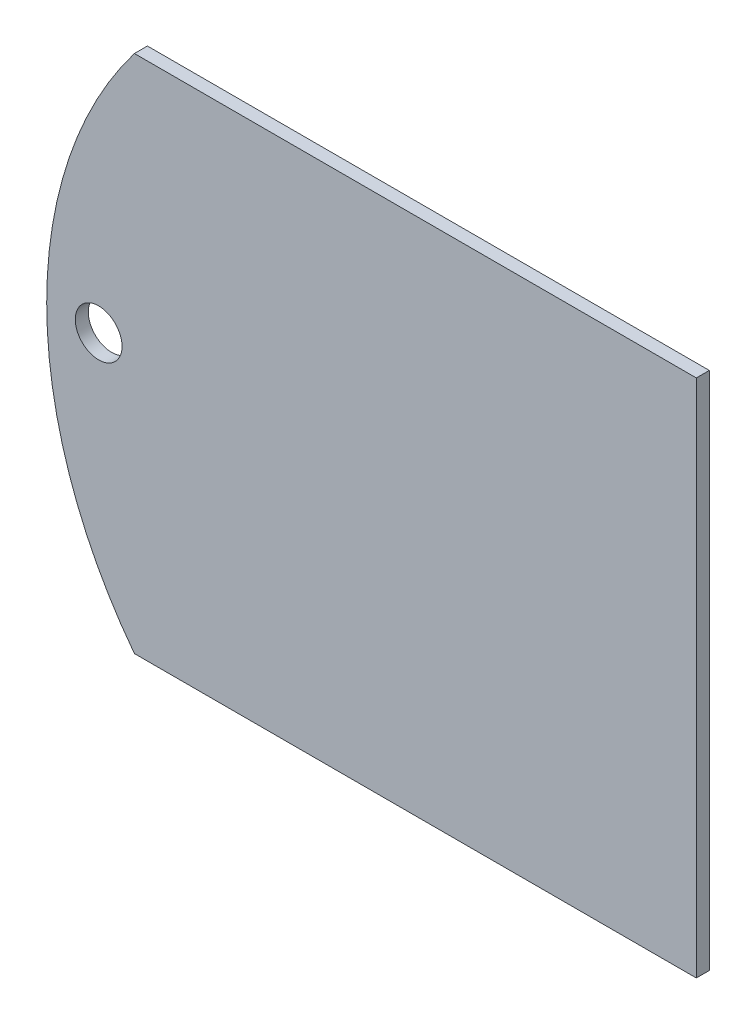
SolidWorks part; units mm, degrees
material "PEI"
ref_plane "Alzado" through (0, 0, 0) normal (0, 0, 1) x (1, 0, 0)
ref_plane "Planta" through (0, 0, 0) normal (0, 1, 0) x (1, 0, 0)
ref_plane "Vista lateral" through (0, 0, 0) normal (1, 0, 0) x (0, 0, -1)
sketch "Croquis1" plane through (0, 0, 0) normal (0, 0, 1) x (1, 0, 0)
  line L0 (-33, -20) -> (-33, 20) construction
  line L1 (0, 0) -> (0, 22.8374) construction
  line L2 (-26.2488, -20) -> (17, -20)
  line L3 (17, -20) -> (17, 20)
  line L4 (17, 20) -> (-33, 20)
  arc A0 (-26.2488, 20) -> (-26.2488, -20) centre (0, 0) ccw
  circle A1 centre (-29, 0) radius 1.8
  circle A2 centre (0, 0) radius 29 construction
  dimension "D1" = 66
  dimension "D5" = 4
  dimension "D6" = 3.6
  dimension "D2" = 20
  dimension "D3" = 20
  dimension "D4" = 50
extrude "Saliente-Extruir1" add sketch "Croquis1" along normal blind 1 contours L4 A0 L2 L3 region at (-6.8483, 0, 0)
